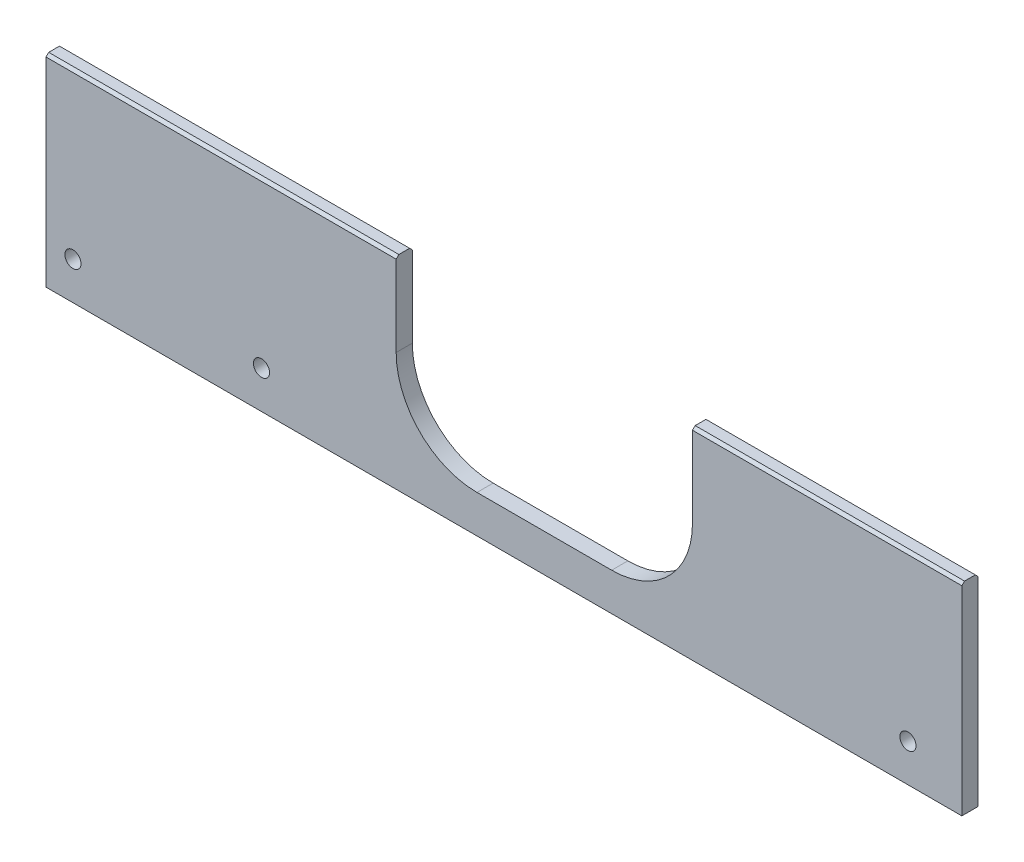
SolidWorks part; units mm, degrees
ref_plane "前视基准面" through (0, 0, 0) normal (0, 0, 1) x (1, 0, 0)
ref_plane "上视基准面" through (0, 0, 0) normal (0, 1, 0) x (1, 0, 0)
ref_plane "右视基准面" through (0, 0, 0) normal (1, 0, 0) x (0, 0, -1)
other "Configuration Table"
sketch "草图1" plane through (0, 0, 0) normal (0, 0, 1) x (1, 0, 0)
  line L1 (-100, 15) -> (70, 15)
  line L2 (-100, 15) -> (-100, -22.5)
  line L3 (-100, -22.5) -> (70, -22.5)
  line L4 (70, 15) -> (70, -22.5)
  dimension "D1" = 170
  dimension "D2" = 37.5
  dimension "D3" = 15
  dimension "D4" = 100
extrude "凸台-拉伸1" add sketch "草图1" along normal blind 3
sketch "草图2" plane through (0, 0, 3) normal (0, 0, 1) x (1, 0, 0)
  circle A0 centre (60, -15.5) radius 1.5
  circle A1 centre (-60, -15.5) radius 1.5
  dimension "D1" = 3
  dimension "D2" = 3
  dimension "D3" = 120
  dimension "D4" = 60
  dimension "D5" = 15.5
extrude "切除-拉伸1" cut sketch "草图2" against normal blind 3
sketch "草图3" plane through (0, 0, 3) normal (0, 0, 1) x (1, 0, 0)
  line L0 (-20, -0.5) -> (5, -0.5) construction
  line L2 (-20, -15.5) -> (5, -15.5)
  line L3 (-35, -0.5) -> (-35, 15)
  line L4 (70, 15) -> (-100, 15) construction
  line L5 (-35, 15) -> (20, 15)
  line L6 (20, 15) -> (20, -0.5)
  arc A0 (-35, -0.5) -> (-20, -15.5) centre (-20, -0.5) ccw
  arc A1 (5, -15.5) -> (20, -0.5) centre (5, -0.5) ccw
  point P2 (-7.5, -0.5)
  dimension "D1" = 15
  dimension "D2" = 0.5
  dimension "D3" = 25
  dimension "D4" = 20
extrude "切除-拉伸2" cut sketch "草图3" against normal blind 3
sketch "草图4" plane through (0, 0, 3) normal (0, 0, 1) x (1, 0, 0)
  circle A0 centre (-95, -15.5) radius 1.5
  circle A1 centre (-60, -15.5) radius 1.5 construction
  dimension "D1" = 35
  dimension "D2" = 3
  dimension "D3" = 15.5
extrude "切除-拉伸3" cut sketch "草图4" against normal blind 3
chamfer "倒角1" distance 0.5 angle 45 4 edges at (45, 15, 0) (-67.5, 15, 0) (45, 15, 3) (-67.5, 15, 3)
